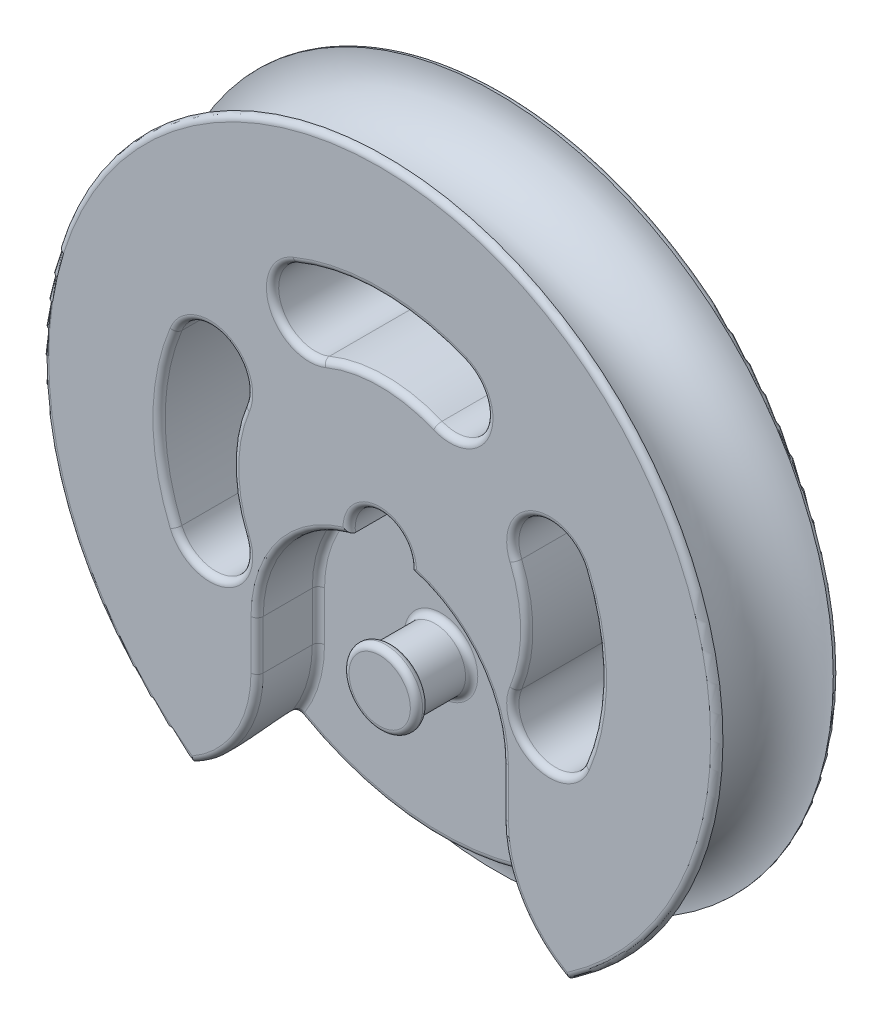
SolidWorks part; units mm, degrees
ref_plane "Front Plane" through (0, 0, 0) normal (0, 0, 1) x (1, 0, 0)
ref_plane "Top Plane" through (0, 0, 0) normal (0, 1, 0) x (1, 0, 0)
ref_plane "Right Plane" through (0, 0, 0) normal (1, 0, 0) x (0, 0, -1)
sketch "Sketch1" plane through (0, 0, 0) normal (0, 0, 1) x (1, 0, 0)
  line L0 (0, 0) -> (0, 27.5) construction
  line L1 (0, 0) -> (-5.7403, 13.8582) construction
  line L2 (0, 0) -> (5.7403, 13.8582) construction
  circle A0 centre (0, 0) radius 2.5
  circle A1 centre (0, 0) radius 27.5
  arc A2 (5.7403, 13.8582) -> (-5.7403, 13.8582) centre (0, 0) ccw construction
  arc A3 (6.8883, 16.6298) -> (-6.8883, 16.6298) centre (0, 0) ccw
  arc A4 (4.5922, 11.0866) -> (-4.5922, 11.0866) centre (0, 0) ccw
  arc A5 (4.5922, 11.0866) -> (6.8883, 16.6298) centre (5.7403, 13.8582) ccw
  arc A6 (-6.8883, 16.6298) -> (-4.5922, 11.0866) centre (-5.7403, 13.8582) ccw
  arc A7 (13.8582, -5.7403) -> (13.8582, 5.7403) centre (0, 0) ccw construction
  arc A8 (16.6298, -6.8883) -> (16.6298, 6.8883) centre (0, 0) ccw
  arc A9 (11.0866, -4.5922) -> (11.0866, 4.5922) centre (0, 0) ccw
  arc A10 (11.0866, -4.5922) -> (16.6298, -6.8883) centre (13.8582, -5.7403) ccw
  arc A11 (16.6298, 6.8883) -> (11.0866, 4.5922) centre (13.8582, 5.7403) ccw
  arc A12 (-5.7403, -13.8582) -> (5.7403, -13.8582) centre (0, 0) ccw construction
  arc A13 (-6.8883, -16.6298) -> (6.8883, -16.6298) centre (0, 0) ccw construction
  arc A14 (-4.5922, -11.0866) -> (4.5922, -11.0866) centre (0, 0) ccw construction
  arc A15 (-4.5922, -11.0866) -> (-6.8883, -16.6298) centre (-5.7403, -13.8582) ccw construction
  arc A16 (6.8883, -16.6298) -> (4.5922, -11.0866) centre (5.7403, -13.8582) ccw construction
  arc A17 (-13.8582, 5.7403) -> (-13.8582, -5.7403) centre (0, 0) ccw construction
  arc A18 (-16.6298, 6.8883) -> (-16.6298, -6.8883) centre (0, 0) ccw
  arc A19 (-11.0866, 4.5922) -> (-11.0866, -4.5922) centre (0, 0) ccw
  arc A20 (-11.0866, 4.5922) -> (-16.6298, 6.8883) centre (-13.8582, 5.7403) ccw
  arc A21 (-16.6298, -6.8883) -> (-11.0866, -4.5922) centre (-13.8582, -5.7403) ccw
  point P7 (0, 15)
  point P20 (15, 0)
  point P27 (0, -15)
  point P34 (-15, 0)
  point P39 (0, 0)
  dimension "D1" = 5
  dimension "D2" = 55
  dimension "D3" = 45
  dimension "D4" = 3
  dimension "D5" = 15
  dimension "D6" = 4
extrude "Boss-Extrude1" add sketch "Sketch1" along normal blind 10
sketch "Sketch2" plane through (0, 0, 0) normal (0, 1, 0) x (1, 0, 0)
  line L0 (0, 0) -> (0, -10) construction
  line L1 (27.5, 0) -> (-27.5, 0) construction
  line L2 (-27.5, -10) -> (27.5, -10) construction
  line L3 (0, -5) -> (-27.5, -5) construction
  line L4 (-27.5, 0) -> (-27.5, -10) construction
  circle A0 centre (-27.5, -5) radius 4.5
  dimension "D1" = 9
revolve "Cut-Revolve1" cut sketch "Sketch2" angle 360 about L0
sketch "Sketch3" plane through (0, 0, 10) normal (0, 0, 1) x (1, 0, 0)
  line L0 (0, 0) -> (0, -27.5) construction
  line L1 (-10, -10) -> (-10, -14)
  line L2 (10, -10) -> (10, -14)
  circle A0 centre (0, 0) radius 27.5 construction
  arc A1 (10, -10) -> (-10, -10) centre (0, -10) ccw
  arc A2 (-10, -14) -> (-15.3201, -22.8373) centre (-20, -14) cw
  arc A3 (10, -14) -> (15.3201, -22.8373) centre (20, -14) ccw
  arc A4 (-15.3201, -22.8373) -> (15.3201, -22.8373) centre (0, 0) ccw
  dimension "D1" = 20
  dimension "D3" = 10
  dimension "D2" = 4
extrude "Cut-Extrude1" cut sketch "Sketch3" against normal blind 5
sketch "Sketch4" plane through (0, 0, 5) normal (0, 0, 1) x (1, 0, 0)
  line L0 (0, 0) -> (0, -27.5) construction
  circle A0 centre (0, 0) radius 27.5 construction
  circle A1 centre (0, -10) radius 2.5
  dimension "D1" = 5
  dimension "D2" = 10
extrude "Boss-Extrude2" add sketch "Sketch4" along normal blind 4
sketch "Sketch5" plane through (0, 0, 9) normal (0, 0, 1) x (1, 0, 0)
  circle A0 centre (0, -10) radius 3
  dimension "D1" = 6
extrude "Boss-Extrude3" add sketch "Sketch5" along normal up to surface (1 mm away) up to face at (0, -5.0065, 10)
fillet "Fillet1" radius 0.5 37 edges at (-12, 0, 0) (-12.7101, -8.5119, 0) (-18, 0, 0) (-12.7101, 8.5119, 0) (0, 12, 0) (-8.5119, 12.7101, 0) (0, 18, 0) (8.5119, 12.7101, 0) (27.5, 0, 0) (2.5, 0, 0) (12, 0, 0) (12.7101, 8.5119, 0) (18, 0, 0) (12.7101, -8.5119, 0) (-12.7101, -8.5119, 10) (-12, 0, 10) (-12.7101, 8.5119, 10) (-18, 0, 10) (12.7101, 8.5119, 10) (12, 0, 10) (12.7101, -8.5119, 10) (18, 0, 10) (-8.5119, 12.7101, 10) (0, 12, 10) (8.5119, 12.7101, 10) (0, 18, 10) (0, 2.5, 10) (-7.8995, -3.8683, 10) (-10, -12, 10) (-11.4327, -19.1576, 10) (0, 27.5, 10) (11.4327, -19.1576, 10) (10, -12, 10) (7.8995, -3.8683, 10) (3, -10, 9) (2.5, -10, 5) (3, -10, 10)
fillet "Fillet2" radius 0.5 9 edges at (12.9864, -21.1281, 8.6) (-12.4089, -20.5096, 7.7926) (0, -23, 5) (10.463, -17.0077, 5) (10, -12, 5) (-7.8995, -3.8683, 5) (-10, -12, 5) (7.8995, -3.8683, 5) (-10.463, -17.0077, 5)
